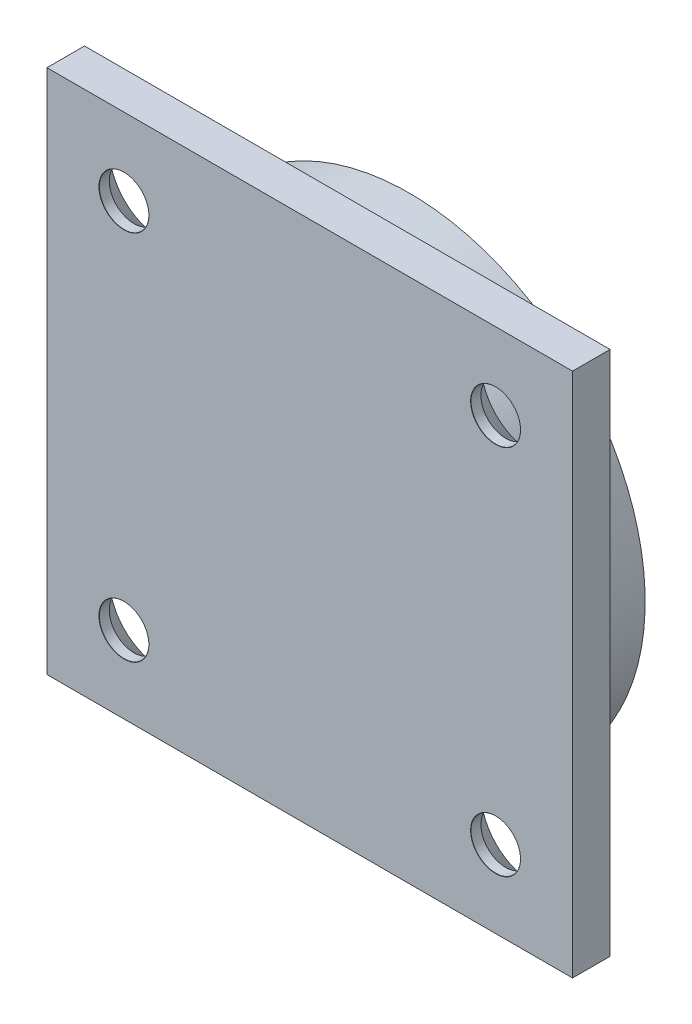
SolidWorks part; units mm, degrees
ref_plane "Ön Düzlem" through (0, 0, 0) normal (0, 0, 1) x (1, 0, 0)
ref_plane "Üst Düzlem" through (0, 0, 0) normal (0, 1, 0) x (1, 0, 0)
ref_plane "Sağ Düzlem" through (0, 0, 0) normal (1, 0, 0) x (0, 0, -1)
sketch "Çizim1" plane through (0, 0, 0) normal (0, 0, 1) x (1, 0, 0)
  circle A0 centre (0, 0) radius 16.075
  circle A1 centre (0, 0) radius 22.5
  circle A2 centre (0, 0) radius 31.425
  circle A3 centre (0, 0) radius 29.425
  dimension "D1" = 32.15
  dimension "D2" = 45
  dimension "D3" = 62.85
  dimension "D4" = 58.85
extrude "Yükseklik-Ekstrüzyon1" add sketch "Çizim1" along normal blind 8.25 contours A1 A0 | A2 A3 region at (-21.8636, 0, 0) region at (-30.5362, 0, 0)
sketch "Çizim2" plane through (0, 0, 8.25) normal (0, 0, 1) x (1, 0, 0)
  line L1 (-35, 35) -> (35, 35)
  line L2 (-35, 35) -> (-35, -35)
  line L3 (-35, -35) -> (35, -35)
  line L4 (35, 35) -> (35, -35)
  line L5 (-35, 35) -> (35, -35) construction
  line L6 (-35, -35) -> (35, 35) construction
  circle A0 centre (-24.75, 24.75) radius 2
  circle A1 centre (24.75, 24.75) radius 2
  circle A2 centre (24.75, -24.75) radius 2
  circle A3 centre (-24.75, -24.75) radius 2
  point P0 (0, 0)
  point P8 (40.2796, 27.2379)
  point P9 (0, 0)
  point P17 (0, 0)
  dimension "D3" = 4
  dimension "D4" = 10.25
  dimension "D5" = 10.25
  dimension "D1" = 70
  dimension "D2" = 70
  dimension "D6" = 4
extrude "Yükseklik-Ekstrüzyon2" add sketch "Çizim2" along normal blind 5
hole_wizard "M6 Altıgen Alyan Havşa Başlı Vida İçin Havşa1" positions "3B Çizim1" profile "Çizim3" countersink size "M6" standard "DIN" end condition through all
sketch3d "3B Çizim1"
  line L0 (-24.75, -24.75, 13.25) -> (-24.75, -24.75, 8.25) construction
  line L1 (24.75, -24.75, 13.25) -> (24.75, -24.75, 8.25) construction
  line L2 (-24.75, 24.75, 13.25) -> (-24.75, 24.75, 8.25) construction
  line L3 (24.75, 24.75, 13.25) -> (24.75, 24.75, 8.25) construction
  point P0 (-24.75, -24.75, 8.25)
  point P4 (24.75, -24.75, 8.25)
  point P8 (-24.75, 24.75, 8.25)
  point P12 (24.75, 24.75, 8.25)
sketch "Çizim3" plane through (-24.75, -24.75, 8.25) normal (1, 0, 0) x (0, 1, 0)
  line L0 (0, 0) -> (0, 5)
  line L1 (0, 5) -> (3.325, 5)
  line L2 (3.3, 4.975) -> (3.3, 3.655)
  line L3 (3.3, 3.655) -> (6.955, 0)
  line L5 (6.955, 0) -> (0, 0)
  line L6 (-3.3, 3.655) -> (-6.955, 0) construction
  line L7 (3.325, 5) -> (3.3, 4.975)
  line L8 (-3.325, 5) -> (-3.3, 4.975) construction
  line L11 (0, -6.35) -> (0, 107.95) construction
  dimension "Thru Hole Dia." = 6.6
  dimension "Thru Hole Depth" = 5
  dimension "Near C'Sink Dia." = 13.91
  dimension "Near C'Sink Angle" = 90
  dimension "Far C'Sink Dia." = 6.65
  dimension "Far C'Sink Angle" = 90
sketch "Çizim4" plane through (0, 0, 0) normal (0, 0, -1) x (-1, 0, 0)
  circle A0 centre (-24.75, -24.75) radius 6.955
  arc A1 (-17.9434, -23.3209) -> (-23.3209, -17.9434) centre (-24.75, -24.75) ccw construction
  circle A2 centre (-24.75, 24.75) radius 6.955
  circle A3 centre (24.75, 24.75) radius 6.955
  circle A4 centre (24.75, -24.75) radius 6.955
  point P14 (0, 0)
  dimension "D1" = 4
extrude "Kes-Ekstrüzyon1" cut sketch "Çizim4" against normal up to surface (8.25 mm away) up to face at (0, 0, 8.25)
